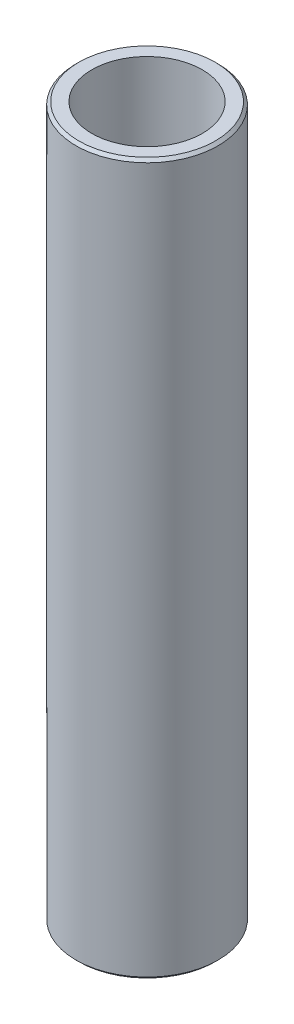
SolidWorks part; units mm, degrees
ref_plane "Front Plane" through (0, 0, 0) normal (0, 0, 1) x (1, 0, 0)
ref_plane "Top Plane" through (0, 0, 0) normal (0, 1, 0) x (1, 0, 0)
ref_plane "Right Plane" through (0, 0, 0) normal (1, 0, 0) x (0, 0, -1)
sketch "Sketch1" plane through (0, 0, 0) normal (0, 1, 0) x (1, 0, 0)
  circle A0 centre (0, 0) radius 37.5
  dimension "SHAFT_OD" = 75
extrude "Boss-Extrude1" add sketch "Sketch1" along normal blind 375.3194
sketch "Sketch2" plane through (0, 0, 0) normal (0, 1, 0) x (1, 0, 0)
  circle A0 centre (0, 0) radius 29.1786
  dimension "BORE_D" = 58.3572
extrude "Cut-Extrude1" cut sketch "Sketch2" along normal through all
chamfer "Chamfer1" distance 1.4798 angle 45 2 edges at (0, 375.3194, 37.5) (0, 0, 37.5)
